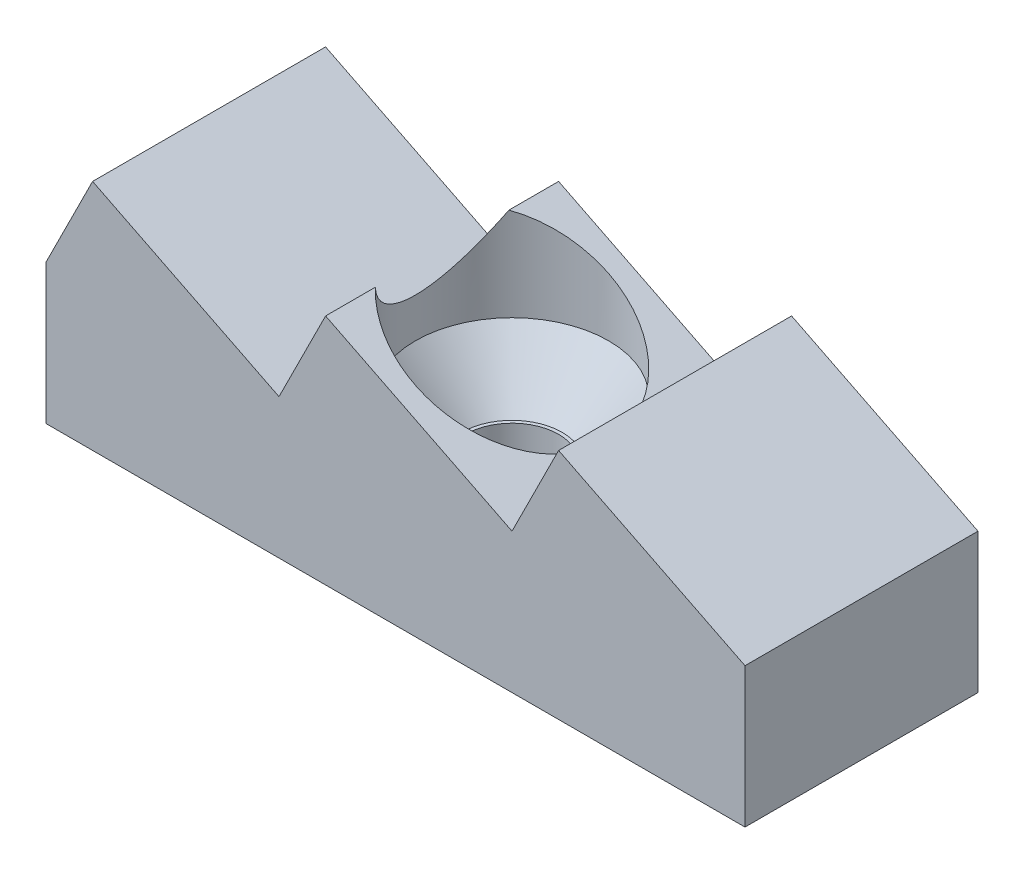
SolidWorks part; units mm, degrees
ref_plane "前视基准面" through (0, 0, 0) normal (0, 0, 1) x (1, 0, 0)
ref_plane "上视基准面" through (0, 0, 0) normal (0, 1, 0) x (1, 0, 0)
ref_plane "右视基准面" through (0, 0, 0) normal (1, 0, 0) x (0, 0, -1)
other "Configuration Table"
sketch "草图1" plane through (0, 0, 0) normal (0, 1, 0) x (1, 0, 0)
  line L0 (-5, 0) -> (5, 0) construction
  line L1 (-7.5, 2.5) -> (7.5, 2.5)
  line L2 (-7.5, 2.5) -> (-7.5, -2.5)
  line L3 (-7.5, -2.5) -> (7.5, -2.5)
  line L4 (7.5, 2.5) -> (7.5, -2.5)
  line L5 (-7.5, 2.5) -> (7.5, -2.5) construction
  line L6 (-7.5, -2.5) -> (7.5, 2.5) construction
  circle A0 centre (0, 0) radius 1
  circle A1 centre (5, 0) radius 2.1
  circle A2 centre (-5, 0) radius 2.1
  point P0 (0, 0)
  point P9 (0, 0)
  dimension "D3" = 2
  dimension "D4" = 4.2
  dimension "D1" = 5
  dimension "D2" = 15
  dimension "D5" = 10
extrude "凸台-拉伸1" add sketch "草图1" along normal blind 3 contours L4 L1 L2 L3 A2 A1 A0 | A2 | A1 | A0 region at (0, 0, -2.3419) region at (0, 0, 0) region at (5, 0, 0) region at (-5, 0, 0)
sketch "草图2" plane through (0, 0, 0) normal (0, 0, 1) x (1, 0, 0)
  line L0 (7.5, 3) -> (3.5, 5)
  line L1 (3.5, 5) -> (2.5, 3)
  line L2 (-7.5, 3) -> (7.5, 3) construction
  line L3 (2.5, 3) -> (7.5, 3)
  line L4 (-2.5, 3) -> (2.5, 3)
  line L5 (2.5, 3) -> (-1.5, 5)
  line L6 (-1.5, 5) -> (-2.5, 3)
  line L7 (-7.5, 3) -> (-2.5, 3)
  line L8 (-2.5, 3) -> (-6.5, 5)
  line L9 (-6.5, 5) -> (-7.5, 3)
  dimension "D1" = 5
  dimension "D2" = 2
  dimension "D4" = 5
  dimension "D3" = 3
extrude "凸台-拉伸2" add sketch "草图2" along normal mid plane 5 contours L8 L9 L7 | L5 L6 L4 | L1 L3 L0 region at (4.5, 3.6667, 0) region at (-5.5, 3.6667, 0) region at (-0.5, 3.6667, 0)
extrude "切除-拉伸1" cut sketch "草图1<3>" along normal through all contours A0 region at (0, 0, 0)
sketch "草图1<3>" plane through (0, 0, 0) normal (0, 1, 0) x (1, 0, 0) same geometry as "草图1"
extrude "切除-拉伸2" cut sketch "草图1<4>" along normal blind 1.4 contours A2 | A1 region at (5, 0, 0) region at (-5, 0, 0)
sketch "草图1<4>" plane through (0, 0, 0) normal (0, 1, 0) x (1, 0, 0) same geometry as "草图1"
sketch "草图4" plane through (0, 0, 0) normal (0, 0, 1) x (1, 0, 0)
  line L0 (0, 0) -> (0, 50000) construction
  line L1 (0, 1.8) -> (1.075, 1.8)
  line L2 (1.075, 1.8) -> (2.075, 3)
  line L3 (2.075, 3) -> (0, 3)
  line L4 (0, 3) -> (0, 1.8)
  line L5 (2.075, 3) -> (2.075, 5)
  line L6 (2.075, 5) -> (0, 5)
  line L7 (0, 5) -> (0, 3)
  dimension "D1" = 1.2
  dimension "D2" = 2.15
  dimension "D3" = 4.15
revolve "切除-旋转1" cut sketch "草图4" angle 360 about L0 region at (0.814, 2.4635, 0) region at (1.0375, 4, 0)
sketch "草图5" plane through (0, 0, 0) normal (0, -1, 0) x (1, 0, 0)
  circle A0 centre (0, 0) radius 2.075
  dimension "D1" = 4.15
extrude "切除-拉伸3" cut sketch "草图5" against normal blind 1
